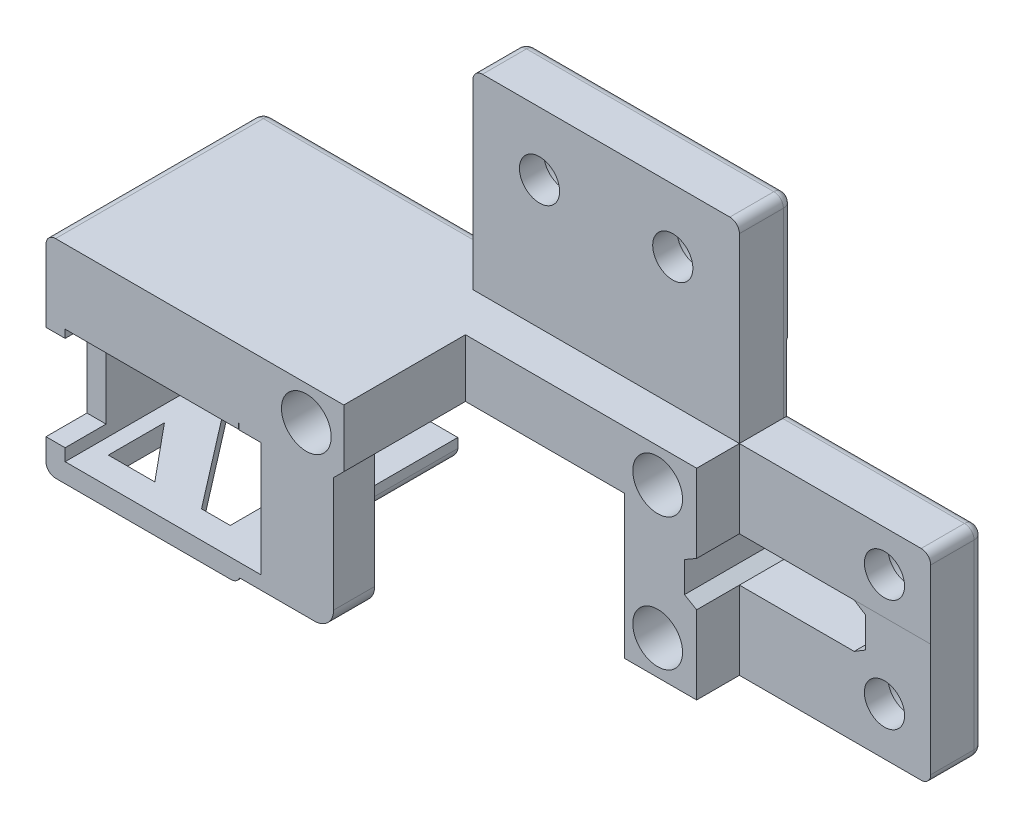
SolidWorks part; units mm, degrees
ref_plane "Piano frontale" through (0, 0, 0) normal (0, 0, 1) x (1, 0, 0)
ref_plane "Piano superiore" through (0, 0, 0) normal (0, 1, 0) x (1, 0, 0)
ref_plane "Piano destro" through (0, 0, 0) normal (1, 0, 0) x (0, 0, -1)
sketch "Schizzo1" plane through (0, 0, 0) normal (0, 0, 1) x (1, 0, 0)
  line L0 (-12.4208, 10.0978) -> (-4.8948, 10.0978)
  line L1 (-4.8948, 10.0978) -> (-4.8948, -4.8482)
  line L2 (-4.8948, -4.8482) -> (11.7472, -4.8482)
  line L3 (11.7472, -4.8482) -> (12.8072, -3.7882)
  line L4 (12.8072, -3.7882) -> (19.3792, -3.7882)
  line L5 (19.3792, -3.7882) -> (19.3792, -10.8902)
  line L6 (19.3792, -10.8902) -> (-12.4208, -10.8902)
  line L7 (-12.4208, -10.8902) -> (-12.4208, -2.7206)
  line L8 (-12.4208, -2.7206) -> (-11.1488, -1.9862)
  line L9 (-11.1488, -1.9862) -> (-11.1488, 1.1938)
  line L10 (-11.1488, 1.1938) -> (-12.4208, 1.9282)
  line L11 (-12.4208, 1.9282) -> (-12.4208, 10.0978)
  circle A0 centre (-8.3448, -7.3348) radius 0.6
  circle A1 centre (-8.3448, 6.517) radius 0.6
  circle A2 centre (15.6634, -7.3348) radius 0.6
  circle A3 centre (-8.3448, 6.517) radius 2.6
  circle A4 centre (-8.3448, -7.3348) radius 2.6
  circle A5 centre (15.6634, -7.3348) radius 2.6
extrude "Estrusione-Estrusione2" add sketch "Schizzo1" along normal blind 10 contours L11 L10 L9 L8 L7 L6 L5 L4 L3 L2 L1 L0 A5 A4 A3 region at (-8.6578, 9.7168, 0)
sketch "Schizzo3" plane through (0, 0, 0) normal (0, 0, -1) x (-1, 0, 0)
  circle A0 centre (-15.6634, -7.3348) radius 2.6
  circle A1 centre (8.3448, -7.3348) radius 2.6
  circle A2 centre (8.3448, 6.517) radius 2.6
  circle A3 centre (8.3448, 6.517) radius 1.1
  circle A4 centre (8.3448, -7.3348) radius 1.1
  circle A5 centre (-15.6634, -7.3348) radius 1.1
extrude "Estrusione-Estrusione3" add sketch "Schizzo3" against normal blind 2
sketch "Schizzo4" plane through (0, 0, 10) normal (0, 0, 1) x (1, 0, 0)
  line L0 (11.7472, -4.8482) -> (11.7472, -10.8902)
  line L1 (19.3792, -10.8902) -> (-12.4208, -10.8902) construction
  line L2 (11.7472, -10.8902) -> (19.3792, -10.8902)
  line L3 (19.3792, -10.8902) -> (19.3792, -3.7882)
  line L4 (19.3792, -3.7882) -> (12.8072, -3.7882)
  line L5 (12.8072, -3.7882) -> (11.7472, -4.8482)
  circle A0 centre (15.6634, -7.3348) radius 2.6
extrude "Estrusione-Estrusione4" add sketch "Schizzo4" along normal blind 12.72
sketch "Schizzo5" plane through (0, -3.7882, 0) normal (0, 1, 0) x (1, 0, 0)
  line L0 (12.8072, -22.72) -> (12.8072, -18.44)
  line L1 (12.8072, -22.72) -> (12.8072, 0) construction
  line L2 (12.8072, -18.44) -> (19.3792, -18.44)
  line L3 (19.3792, -22.72) -> (19.3792, 0) construction
  line L4 (19.3792, -18.44) -> (19.3792, -22.72)
  line L5 (19.3792, -22.72) -> (12.8072, -22.72)
extrude "Estrusione-Estrusione5" add sketch "Schizzo5" along normal blind 14
sketch "Schizzo6" plane through (19.3792, 0, 0) normal (1, 0, 0) x (0, 0, -1)
  line L0 (-22.72, -10.8902) -> (-22.72, 10.2118) construction
  line L1 (-22.72, -3.8698) -> (-18.44, -3.8698)
  line L2 (-22.72, -3.8698) -> (-22.72, 10.2118)
  line L3 (-22.72, 10.2118) -> (-18.44, 10.2118)
  line L4 (-18.44, -3.8698) -> (-18.44, 10.2118)
  line L5 (-22.72, -3.8698) -> (-18.44, 10.2118) construction
  line L6 (-22.72, 10.2118) -> (-18.44, -3.8698) construction
  point P4 (-20.58, 3.171)
extrude "Estrusione-Estrusione6" add sketch "Schizzo6" along normal blind 3.3
sketch "Schizzo7" plane through (19.3792, 0, 0) normal (1, 0, 0) x (0, 0, -1)
  line L1 (-22.72, -10.8902) -> (0, -10.8902)
  line L2 (-22.72, -10.8902) -> (-22.72, -3.7882)
  line L3 (-22.72, -3.7882) -> (0, -3.7882)
  line L4 (0, -10.8902) -> (0, -3.7882)
  line L5 (-22.72, -10.8902) -> (0, -3.7882) construction
  line L6 (-22.72, -3.7882) -> (0, -10.8902) construction
  point P4 (-11.36, -7.3392)
extrude "Estrusione-Estrusione7" add sketch "Schizzo7" along normal blind 23.5
sketch "Schizzo8" plane through (0, -3.7882, 0) normal (0, 1, 0) x (1, 0, 0)
  line L0 (-11.5434, 0) -> (11.5434, 0) construction
  line L1 (42.8792, -22.72) -> (22.7294, -22.72)
  line L2 (42.8792, -22.72) -> (42.8792, 0)
  line L3 (42.8792, 0) -> (22.7294, 0)
  line L4 (22.7294, -22.72) -> (22.7294, 0)
  line L5 (42.8792, -22.72) -> (22.7294, 0) construction
  line L6 (42.8792, 0) -> (22.7294, -22.72) construction
  line L7 (42.8792, -22.72) -> (22.6792, -22.72) construction
  point P4 (32.8043, -11.36)
sketch "Schizzo9" plane through (22.6792, 0, 0) normal (1, 0, 0) x (0, 0, -1)
  circle A0 centre (-20.7064, 3.2118) radius 0.593
extrude "Estrusione-Estrusione9" add sketch "Schizzo8" along normal blind 0.6
sketch "Schizzo11" plane through (0, -3.1882, 0) normal (0, 1, 0) x (1, 0, 0)
  line L0 (-11.6061, 0) -> (11.6061, 0) construction
  line L1 (42.8792, -22.72) -> (40.8792, -22.72)
  line L2 (42.8792, -22.72) -> (42.8792, 0)
  line L3 (42.8792, 0) -> (40.8792, 0)
  line L4 (40.8792, -22.72) -> (40.8792, 0)
  line L5 (42.8792, -22.72) -> (40.8792, 0) construction
  line L6 (42.8792, 0) -> (40.8792, -22.72) construction
  point P4 (41.8792, -11.36)
extrude "Estrusione-Estrusione10" add sketch "Schizzo11" along normal blind 14
sketch "Schizzo12" plane through (40.8792, 0, 0) normal (-1, 0, 0) x (0, 0, 1)
  line L0 (22.72, 10.8118) -> (22.72, -3.1882) construction
  line L1 (0, 10.8118) -> (22.72, 10.8118)
  line L2 (0, 10.8118) -> (0, 8.8118)
  line L3 (0, 8.8118) -> (22.72, 8.8118)
  line L4 (22.72, 10.8118) -> (22.72, 8.8118)
  line L5 (0, 10.8118) -> (22.72, 8.8118) construction
  line L6 (0, 8.8118) -> (22.72, 10.8118) construction
  point P4 (11.36, 9.8118)
extrude "Estrusione-Estrusione11" add sketch "Schizzo12" along normal blind 18.33
sketch "Schizzo13" plane through (42.8792, 0, 0) normal (1, 0, 0) x (0, 0, -1)
  line L0 (-22.72, 10.8118) -> (-22.72, -10.8902) construction
  line L1 (-22.72, 7.5469) -> (-18.44, 7.5469)
  line L2 (-22.72, 7.5469) -> (-22.72, -2.3493)
  line L3 (-22.72, -2.3493) -> (-18.44, -2.3493)
  line L4 (-18.44, 7.5469) -> (-18.44, -2.3493)
  line L5 (-22.72, 7.5469) -> (-18.44, -2.3493) construction
  line L6 (-22.72, -2.3493) -> (-18.44, 7.5469) construction
  point P4 (-20.58, 2.5988)
sketch "Schizzo14" plane through (0, 10.8118, 0) normal (0, 1, 0) x (1, 0, 0)
  line L0 (26.4779, -7.2269) -> (39.2183, -7.2269)
  line L1 (39.2183, -7.2269) -> (26.4779, -23.7572)
  line L2 (26.4779, -7.2269) -> (26.4779, -23.7572)
extrude "Taglio-Estrusione3" cut sketch "Schizzo14" against normal blind 10
sketch "Schizzo15" plane through (0, 10.8118, 0) normal (0, 1, 0) x (1, 0, 0)
  line L0 (39.2183, -14.0003) -> (27.123, -28.5953)
  line L1 (27.123, -28.5953) -> (39.2183, -28.5953)
  line L2 (39.2183, -28.5953) -> (39.2183, -14.0003)
extrude "Taglio-Estrusione4" cut sketch "Schizzo15" against normal blind 10
sketch "Schizzo16" plane through (0, -10.8902, 0) normal (0, -1, 0) x (-1, 0, 0)
  line L0 (-15.4404, 0) -> (-15.4404, -0.5309)
  line L1 (-42.8792, 0) -> (12.4208, 0) construction
  line L2 (12.4208, -10) -> (12.4208, 0) construction
  line L3 (-15.4404, -0.5309) -> (12.4208, -0.5309)
  line L4 (-15.4404, -0.5309) -> (-15.4404, -5.5309)
  line L5 (-15.4404, -5.5309) -> (12.4208, -5.5309)
  line L6 (12.4208, -0.5309) -> (12.4208, -5.5309)
  line L7 (-15.4404, -0.5309) -> (12.4208, -5.5309) construction
  line L8 (-15.4404, -5.5309) -> (12.4208, -0.5309) construction
  point P7 (-1.5098, -3.0309)
extrude "Estrusione-Estrusione12" add sketch "Schizzo16" along normal blind 20 contours L4 L3 L6 L5
sketch "Schizzo17" plane through (0, 0, 0.5309) normal (0, 0, -1) x (-1, 0, 0)
  line L0 (-15.4404, -10.8902) -> (-15.4404, -17.0902)
  line L1 (-15.4404, -30.8902) -> (-15.4404, -10.8902) construction
  line L3 (-15.4404, -17.7308) -> (12.4208, -17.7308)
  line L4 (-15.4404, -17.7308) -> (-15.4404, -30.8902)
  line L5 (-15.4404, -30.8902) -> (12.4208, -30.8902)
  line L6 (12.4208, -17.7308) -> (12.4208, -30.8902)
  line L7 (-15.4404, -17.7308) -> (12.4208, -30.8902) construction
  line L8 (-15.4404, -30.8902) -> (12.4208, -17.7308) construction
  point P9 (-1.5098, -24.3105)
  line M3 (-15.4404, -10.8902) -> (-15.4404, -30.8902)
  line M4 (-15.4404, -30.8902) -> (12.4208, -30.8902)
  line M5 (12.4208, -30.8902) -> (12.4208, -10.8902)
extrude "Estrusione-Estrusione13" add sketch "Schizzo17" along normal blind 0.6 contours L3 M3 M4 M5 region at (1.5098, -24.3105, 0.5309)
sketch "Schizzo18" plane through (0, 0, 5.5309) normal (0, 0, 1) x (1, 0, 0)
  line L0 (-12.4208, -17.7308) -> (-12.4208, -30.8902)
  line L1 (-12.4208, -17.7308) -> (15.4404, -17.7308)
  line L2 (1.5098, -17.7308) -> (1.5098, -30.8902)
  line L3 (15.4404, -30.8902) -> (-12.4208, -30.8902) construction
  line L4 (1.5098, -30.8902) -> (-12.4208, -30.8902)
  line L5 (1.5098, -30.8902) -> (15.4404, -30.8902)
  circle A0 centre (-5.4555, -24.3105) radius 2.1
  circle A1 centre (8.4751, -24.3105) radius 2.1
  circle A2 centre (-5.4555, -24.3105) radius 3.6
  circle A3 centre (8.4751, -24.3105) radius 3.6
extrude "Taglio-Estrusione5" cut sketch "Schizzo18" against normal through all contours A1 | A0
sketch "Schizzo19" plane through (0, 0, -0.0691) normal (0, 0, -1) x (-1, 0, 0)
  circle A0 centre (-8.4751, -24.3105) radius 3.6
  circle A1 centre (5.4555, -24.3105) radius 3.6
  circle A2 centre (-8.4751, -24.3105) radius 2.1
  circle A3 centre (5.4555, -24.3105) radius 2.1
extrude "Taglio-Estrusione7" cut sketch "Schizzo19" against normal blind 3.05
sketch "Schizzo21" plane through (-12.4208, 0, 0) normal (-1, 0, 0) x (0, 0, 1)
  line L5 (10, 1.9282) -> (0, 1.9282) construction
  line L6 (0, 10.0978) -> (5.531, 10.0978)
  line L7 (0, 10.0978) -> (0, 1.9282)
  line L15 (0, 1.9282) -> (5.531, 1.9282)
  line L16 (5.531, 10.0978) -> (5.531, 1.9282)
  line L17 (0, 10.0978) -> (5.531, 1.9282) construction
  line L18 (0, 1.9282) -> (5.531, 10.0978) construction
  line L19 (5.5309, -2.7206) -> (5.5309, 1.9282)
  line L20 (0, -2.7206) -> (5.5309, -2.7206)
  line L21 (0, -2.7206) -> (0, -10.8902)
  line L22 (0, -10.8902) -> (5.5309, -10.8902)
  line L23 (5.5309, -2.7206) -> (5.5309, -10.8902)
  line L24 (0, -2.7206) -> (5.5309, -10.8902) construction
  line L25 (0, -10.8902) -> (5.5309, -2.7206) construction
  point P4 (2.7655, 6.013)
  point P12 (2.7654, -6.8054)
  line M1 (0, -2.7206) -> (0, -10.8902)
  line M2 (0, -10.8902) -> (0.5309, -10.8902)
  line M10 (10, -2.7206) -> (0, -2.7206)
extrude "Estrusione-Estrusione15" add sketch "Schizzo21" along normal blind 20 contours L16 L6 L7 L15 | L23 L22 M10 M1 M2 region at (-12.4208, -6.8054, 2.7654) region at (-12.4208, 6.013, 2.7655)
sketch "Schizzo22" plane through (0, 1.9282, 0) normal (0, -1, 0) x (1, 0, 0)
  line L0 (-32.4208, 0) -> (-12.4208, 0) construction
  line L1 (-32.4208, 5.531) -> (-24.4208, 5.531)
  line L2 (-32.4208, 5.531) -> (-32.4208, 0)
  line L3 (-32.4208, 0) -> (-24.4208, 0)
  line L4 (-24.4208, 5.531) -> (-24.4208, 0)
  line L5 (-32.4208, 5.531) -> (-24.4208, 0) construction
  line L6 (-32.4208, 0) -> (-24.4208, 5.531) construction
  point P4 (-28.4208, 2.7655)
extrude "Estrusione-Estrusione16" add sketch "Schizzo22" along normal blind 4.65
sketch "Schizzo23" plane through (0, 0, 5.531) normal (0, 0, 1) x (1, 0, 0)
  line L0 (-24.4208, 1.9282) -> (-25.6908, 1.9282)
  line L1 (-24.4208, 1.9282) -> (-24.4208, -2.7218)
  line L2 (-24.4208, -2.7218) -> (-25.5762, -1.9837)
  line L4 (-25.6266, 1.2653) -> (-25.5762, -1.9837)
  line L5 (-25.6257, 1.2048) -> (-24.4208, 1.9282)
  line M13 (-24.4208, -2.7218) -> (-24.4208, 1.9282)
extrude "Taglio-Estrusione8" cut sketch "Schizzo23" against normal through all contours L5 L2 M13 region at (-24.9743, -0.3771, 5.531)
sketch "Schizzo24" plane through (0, 0, 5.531) normal (0, 0, 1) x (1, 0, 0)
  circle A0 centre (-27.5854, 5.1043) radius 2.1
  circle A1 centre (-27.5854, -6.6106) radius 2.1
extrude "Taglio-Estrusione9" cut sketch "Schizzo24" against normal through all
sketch "Schizzo26" plane through (0, 0, 0) normal (0, 0, -1) x (-1, 0, 0)
  circle A0 centre (27.5854, 5.1043) radius 3.6
  circle A1 centre (27.5854, -6.6106) radius 3.6
extrude "Taglio-Estrusione10" cut sketch "Schizzo26" against normal blind 3.05
fillet "Raccordo6" radius 1 12 edges at (-12.4208, -24.3105, -0.0691) (15.4404, -24.3105, -0.0691) (1.5098, -30.8902, -0.0691) (42.8792, -0.0392, 0) (32.7142, 10.8118, 0) (22.5492, 10.8118, 11.36) (42.8792, 10.8118, 11.36) (42.8792, -10.8902, 11.36) (15.4404, -30.8902, 2.7309) (-12.4208, -30.8902, 2.7309) (-32.4208, -10.8902, 2.7654) (-32.4208, 10.0978, 2.7655)
fillet "Raccordo7" radius 1 6 edges at (42.5863, -10.5973, 0.2929) (-18.1578, 10.0978, 0) (-32.1279, 9.8049, 0) (-32.4208, -0.3962, 0) (-32.1279, -10.5973, 0) (5.2292, -10.8902, 0)
sketch "Schizzo27" plane through (0, 0, 0) normal (0, 0, 1) x (1, 0, 0)
  line L0 (-12.4208, 10.0978) -> (-4.8948, 10.0978)
  line L1 (-4.8948, 10.0978) -> (-4.8948, -4.8482)
  line L2 (-4.8948, -4.8482) -> (11.7472, -4.8482)
  line L3 (11.7472, -4.8482) -> (12.8072, -3.7882)
  line L4 (12.8072, -3.7882) -> (19.3792, -3.7882)
  line L5 (19.3792, -3.7882) -> (19.3792, -10.8902)
  line L6 (19.3792, -10.8902) -> (-12.4208, -10.8902)
  line L7 (-12.4208, -10.8902) -> (-12.4208, -2.7206)
  line L8 (-12.4208, -2.7206) -> (-11.1488, -1.9862)
  line L9 (-11.1488, -1.9862) -> (-11.1488, 1.1938)
  line L10 (-11.1488, 1.1938) -> (-12.4208, 1.9282)
  line L11 (-12.4208, 1.9282) -> (-12.4208, 10.0978)
  circle A0 centre (-8.3448, -7.3348) radius 0.6
  circle A1 centre (-8.3448, 6.517) radius 0.6
  circle A2 centre (15.6634, -7.3348) radius 0.6
  circle A3 centre (-8.3448, 6.517) radius 2.6
  circle A4 centre (-8.3448, -7.3348) radius 2.6
  circle A5 centre (15.6634, -7.3348) radius 2.6
sketch "Schizzo28" plane through (22.6792, 0, 0) normal (1, 0, 0) x (0, 0, -1)
  line L0 (-18.44, -3.7882) -> (-18.44, 8.8118) construction
  line L1 (-22.72, 8.8118) -> (-18.44, 8.8118)
  line L2 (-22.72, 8.8118) -> (-22.72, -3.1564)
  line L3 (-22.72, -3.1564) -> (-18.44, -3.1564)
  line L4 (-18.44, 8.8118) -> (-18.44, -3.1564)
  line L5 (-22.72, 8.8118) -> (-18.44, -3.1564) construction
  line L6 (-22.72, -3.1564) -> (-18.44, 8.8118) construction
  point P4 (-20.58, 2.8277)
extrude "Taglio-Estrusione11" cut sketch "Schizzo28" against normal blind 2.3
extrude "Taglio-Estrusione12" cut sketch "Schizzo9" against normal blind 8 contours A0
sketch "Schizzo29" plane through (39.2183, 0, 0) normal (-1, 0, 0) x (0, 0, 1)
  line L0 (22.72, 8.8118) -> (14.0003, 8.8118) construction
  line L1 (22.72, 10.8118) -> (19.862, 10.8118)
  line L2 (22.72, 10.8118) -> (22.72, 8.8118)
  line L3 (22.72, 8.8118) -> (19.862, 8.8118)
  line L4 (19.862, 10.8118) -> (19.862, 8.8118)
  line L5 (22.72, 10.8118) -> (19.862, 8.8118) construction
  line L6 (22.72, 8.8118) -> (19.862, 10.8118) construction
  point P4 (21.291, 9.8118)
extrude "Estrusione-Estrusione17" add sketch "Schizzo29" along normal blind 13
fillet "Raccordo8" radius 2 1 edges at (12.8072, 10.2118, 20.58)
extrude "Taglio-Estrusione13" cut sketch "Schizzo13" against normal blind 13
sketch "Schizzo30" plane through (0, 0, 10) normal (0, 0, 1) x (1, 0, 0)
  line L0 (-12.4208, 10.0978) -> (-4.8948, 10.0978)
  line L1 (-4.8948, 10.0978) -> (-4.8948, -4.8482)
  line L2 (-4.8948, -4.8482) -> (11.7472, -4.8482)
  line L3 (11.7472, -4.8482) -> (12.8072, -3.7882)
  line L4 (12.8072, -3.7882) -> (12.8072, 8.2118)
  line L5 (14.8072, 10.2118) -> (22.6327, 10.2118)
  line L6 (23.5492, 10.8118) -> (41.8792, 10.8118)
  line L7 (42.8792, 9.8118) -> (42.8792, -9.8902)
  line L8 (41.8792, -10.8902) -> (-12.4208, -10.8902)
  line L9 (-12.4208, -10.8902) -> (-12.4208, 10.0978)
  arc A0 (12.8072, 8.2118) -> (14.8072, 10.2118) centre (14.8072, 8.2118) cw
  arc A1 (22.6327, 10.2118) -> (23.5492, 10.8118) centre (23.5492, 9.8118) cw
  arc A2 (42.8792, 9.8118) -> (41.8792, 10.8118) centre (41.8792, 9.8118) ccw construction
  arc A3 (41.8792, 10.8118) -> (42.8792, 9.8118) centre (41.8792, 9.8118) cw
  arc A4 (42.8792, -9.8902) -> (41.8792, -10.8902) centre (41.8792, -9.8902) cw
sketch "Schizzo31" plane through (0, 0, 0) normal (0, 0, -1) x (-1, 0, 0)
  line L0 (11.1488, 1.1938) -> (12.4208, 1.9282)
  line L1 (12.4208, 1.9282) -> (24.4208, 1.9282)
  line L2 (24.4208, 1.9282) -> (25.6257, 1.2048)
  line L3 (25.6257, 1.2048) -> (25.5762, -1.9837)
  line L4 (25.5762, -1.9837) -> (24.4208, -2.7218)
  line L5 (24.4208, -2.7218) -> (12.4208, -2.7206)
  line L6 (12.4208, -2.7206) -> (11.1488, -1.9862)
  line L7 (11.1488, -1.9862) -> (11.1488, 1.1938)
sketch "Schizzo32" plane through (0, 0, 5.531) normal (0, 0, 1) x (1, 0, 0)
  line L0 (-12.4208, 10.0978) -> (-31.4208, 10.0978)
  line L1 (-31.4208, 10.0978) -> (-12.4208, 10.0978) construction
  line L2 (-32.4208, 9.0978) -> (-32.4208, -9.8902)
  line L3 (-31.4208, -10.8902) -> (-12.4208, -10.8902)
  line L4 (-12.4208, -10.8902) -> (-12.4208, -29.8902)
  line L5 (-11.4208, -30.8902) -> (14.4404, -30.8902)
  line L6 (15.4404, -29.8902) -> (15.4404, -10.8902)
  line L7 (19.3792, -10.8902) -> (-12.4208, -10.8902) construction
  line L8 (15.4404, -29.8902) -> (15.4404, -10.8902) construction
  arc A0 (-31.4208, 10.0978) -> (-32.4208, 9.0978) centre (-31.4208, 9.0978) ccw
  arc A1 (-32.4208, -9.8902) -> (-31.4208, -10.8902) centre (-31.4208, -9.8902) ccw
  arc A2 (-12.4208, -29.8902) -> (-11.4208, -30.8902) centre (-11.4208, -29.8902) ccw
  arc A3 (14.4404, -30.8902) -> (15.4404, -29.8902) centre (14.4404, -29.8902) ccw
  circle A4 centre (-27.5854, 5.1043) radius 2.1
  circle A5 centre (-27.5854, -6.6106) radius 2.1
  circle A6 centre (-5.4555, -24.3105) radius 2.1
  circle A7 centre (8.4751, -24.3105) radius 2.1
move or copy body "Corpo-Sposta/copia1" bodies to move or copy 131 copy no rotation origin (5.2292, -10.0392, 0) rotation axis (0, 0, 1) rotation angle 180
